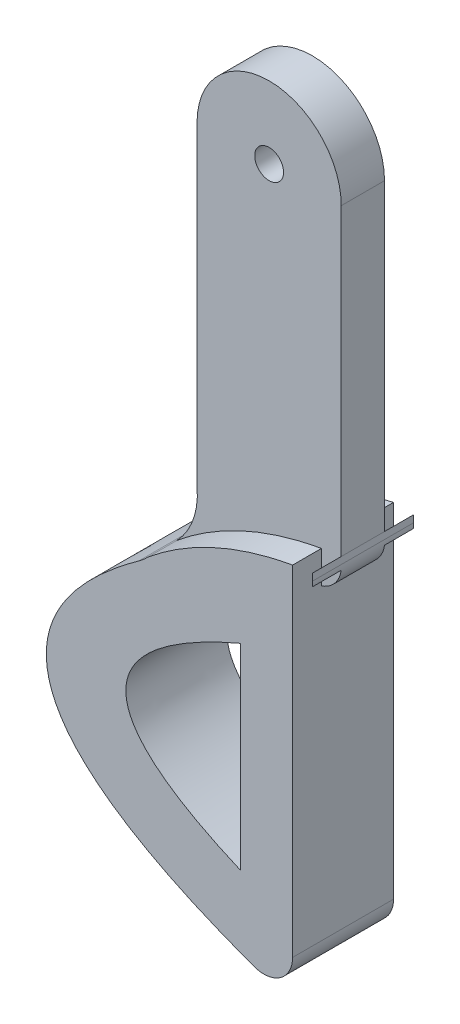
SolidWorks part; units mm, degrees
ref_plane "前视基准面" through (0, 0, 0) normal (0, 0, 1) x (1, 0, 0)
ref_plane "上视基准面" through (0, 0, 0) normal (0, 1, 0) x (1, 0, 0)
ref_plane "右视基准面" through (0, 0, 0) normal (1, 0, 0) x (0, 0, -1)
sketch "草图1" plane through (0, 0, 0) normal (0, 0, 1) x (1, 0, 0)
  line L0 (-5, 0) -> (-5, -18.1113)
  line L1 (-5, -18.1113) -> (5, -18.1113)
  line L2 (5, -18.1113) -> (5, 0)
  arc A0 (5, 0) -> (-5, 0) centre (0, 0) ccw
  circle A1 centre (0, 0) radius 1
  dimension "D1" = 10
  dimension "D2" = 2
extrude "凸台-拉伸1" add sketch "草图1" along normal blind 3
sketch "草图2" plane through (0, 0, 3) normal (0, 0, 1) x (1, 0, 0)
  line L6 (5, -18.1113) -> (5, -21.0686)
  line L7 (3.627, -23.5167) -> (3.627, -47.6476)
  line L8 (-5, -23.815) -> (-2.9643, -23.7446)
  line L9 (3.627, -23.5167) -> (5.0947, -23.4659)
  line L10 (0, -27.7824) -> (0, -41.4014)
  line L13 (-5, -21.0686) -> (-5, -18.1113)
  line L14 (-5, -21.0686) -> (-5, -23.815)
  line L15 (5, -21.0686) -> (5.0947, -23.4659)
  spline S0 degree 3 poles (3.627, -47.6476) (-16.6827, -40.9111) (-18.8797, -32.9434) (-2.9643, -23.7446) knots 0 0 0 0 0.912623 0.912623 0.912623 0.912623
  spline S1 degree 2 poles (0, -41.4014) (-15.8731, -34.5919) (0, -27.7824) knots 0 0 0 1 1 1
extrude "凸台-拉伸2" add sketch "草图2" against normal blind 5 and the other way blind 2
fillet "圆角3" radius 2 3 edges at (5.0947, -23.4659, 1.5) (-5, -23.815, 1.5) (3.627, -47.6476, 1.5)
fillet "圆角4" radius 5 1 edges at (-2.9643, -23.7446, 1.5)
sketch "草图6" plane through (0, 0, 5) normal (0, 0, 1) x (1, 0, 0)
  line L0 (3.627, -21.2692) -> (3.627, -25.8016)
  line L1 (-5, -18.1113) -> (5, -18.1113)
  line L2 (5, -18.1113) -> (5, -25.8016)
  line L3 (5, -25.8016) -> (3.627, -25.8016)
  line L5 (-5, -21.7449) -> (-5, -18.1113) construction
  line L6 (-5, -21.2692) -> (-5, -18.1113)
  line L7 (-5, -21.2692) -> (-7.0534, -26.3643)
  arc A0 (-7.0534, -26.3643) -> (-4.9935, -21.9059) centre (-9.9773, -22.3083) ccw construction
  spline S0 degree 2 poles (3.627, -21.2692) (-2.6239, -22.3889) (-7.0534, -26.3643) knots 0 0 0 1 1 1
extrude "切除-拉伸2" cut sketch "草图6" against normal blind 2
sketch "草图7" plane through (0, 0, -2) normal (0, 0, -1) x (-1, 0, 0)
  line L0 (-3.627, -21.0043) -> (-3.627, -25.8016)
  line L1 (-5, -18.1113) -> (-5, -25.8016)
  line L2 (-5, -25.8016) -> (-3.627, -25.8016)
  line L3 (7.0534, -26.3643) -> (7.0534, -18.1113)
  line L4 (7.0534, -18.1113) -> (-5, -18.1113)
  spline S0 degree 2 poles (-3.627, -21.0043) (2.5776, -22.3609) (7.0534, -26.3643) knots 0 0 0 1 1 1
extrude "切除-拉伸3" cut sketch "草图7" against normal blind 2
